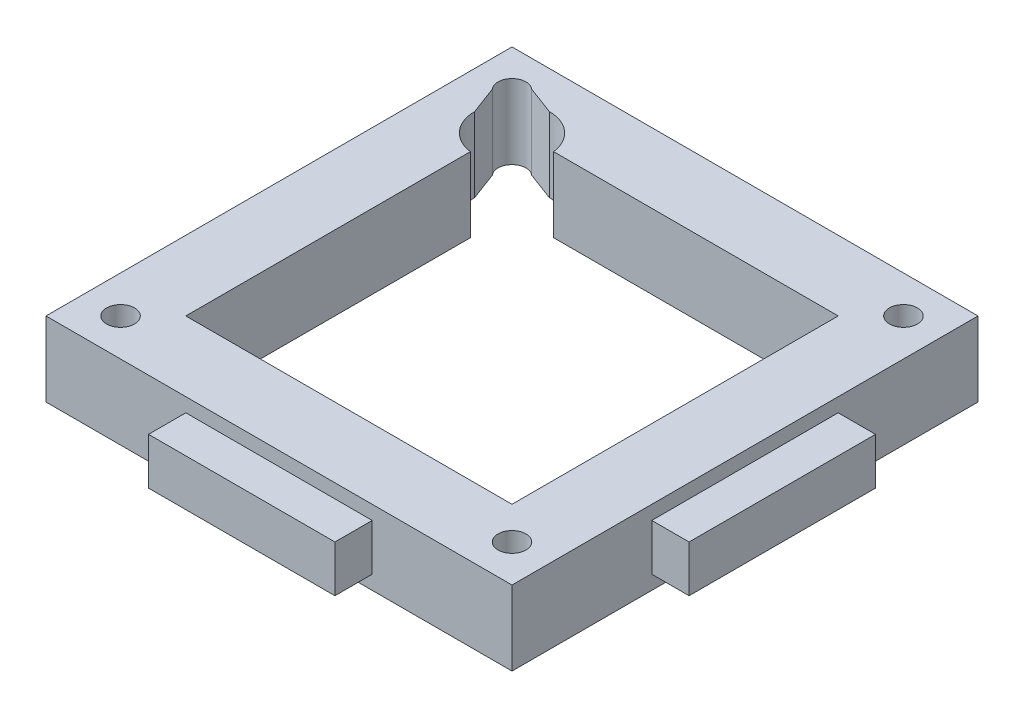
SolidWorks part; units mm, degrees
ref_plane "Front Plane" through (0, 0, 0) normal (0, 0, 1) x (1, 0, 0)
ref_plane "Top Plane" through (0, 0, 0) normal (0, 1, 0) x (1, 0, 0)
ref_plane "Right Plane" through (0, 0, 0) normal (1, 0, 0) x (0, 0, -1)
sketch "Sketch1" plane through (0, 0, 0) normal (0, 1, 0) x (1, 0, 0)
  line L0 (17.5, 17.5) -> (-13.0314, 17.5)
  line L1 (-25, -25) -> (25, -25)
  line L2 (-25, -25) -> (-25, 25)
  line L3 (-25, 25) -> (25, 25)
  line L4 (25, -25) -> (25, 25)
  line L5 (0, 25) -> (0, -25) construction
  line L6 (-25, 0) -> (25, 0) construction
  line L11 (0, 20) -> (0, -20) construction
  line L12 (-20, 0) -> (20, 0) construction
  line L13 (-17.5, -17.5) -> (17.5, -17.5)
  line L16 (17.5, -17.5) -> (17.5, 17.5)
  line L17 (0, 17.5) -> (0, -17.5) construction
  line L18 (-17.5, 0) -> (17.5, 0) construction
  line L19 (-17.5, -17.5) -> (-17.5, 13.0314)
  line L20 (-22.1301, 20.0137) -> (-21, 17)
  line L21 (-20.0137, 22.1301) -> (-17, 21)
  arc A0 (-20.0137, 22.1301) -> (-22.1301, 20.0137) centre (-21, 21) ccw
  circle A1 centre (21, 21) radius 1.5
  circle A2 centre (21, -21) radius 1.5
  circle A3 centre (-21, -21) radius 1.5
  arc A4 (-21, 17) -> (-17, 21) centre (-17, 17) ccw
  point P0 (0, 0)
  point P4 (0, 0)
  point P13 (0, 0)
  dimension "D1" = 50
  dimension "D2" = 50
  dimension "D4" = 35
extrude "Support" add sketch "Sketch1" along normal blind 8 contours L1 L4 L3 L2 A4 L0 L16 L13 L19 L20 A0 L21 A1 A2 A3 region at (-24.2929, 0, 0)
sketch "Sketch2" plane through (0, 0, 0) normal (0, 0, 1) x (1, 0, 0)
  line L4 (-10, 1.5) -> (10, 1.5)
  line L5 (-10, 1.5) -> (-10, 6.5)
  line L6 (-10, 6.5) -> (10, 6.5)
  line L7 (10, 1.5) -> (10, 6.5)
  line L8 (0, 6.5) -> (0, 1.5) construction
  line L9 (-10, 4) -> (10, 4) construction
  point P6 (0, 4)
  dimension "D1" = 20
  dimension "D2" = 5
extrude "South Dowel" add sketch "Sketch2" along normal blind 4 from surface starting at face at (0, 4, 25)
sketch "Sketch3" plane through (0, 0, 0) normal (1, 0, 0) x (0, 0, -1)
  line L4 (-10, 1.5) -> (10, 1.5)
  line L5 (-10, 1.5) -> (-10, 6.5)
  line L6 (-10, 6.5) -> (10, 6.5)
  line L7 (10, 1.5) -> (10, 6.5)
  line L8 (0, 6.5) -> (0, 1.5) construction
  line L9 (-10, 4) -> (10, 4) construction
  point P6 (0, 4)
  dimension "D1" = 20
  dimension "D2" = 5
extrude "East Dowel" add sketch "Sketch3" along normal blind 4 from surface starting at face at (25, 4, 0)
extrude "West Cut" cut sketch "Sketch3<2>" along normal blind 4 from surface starting at face at (-25, 4, 0)
sketch "Sketch3<2>" plane through (0, 0, 0) normal (1, 0, 0) x (0, 0, -1) same geometry as "Sketch3"
